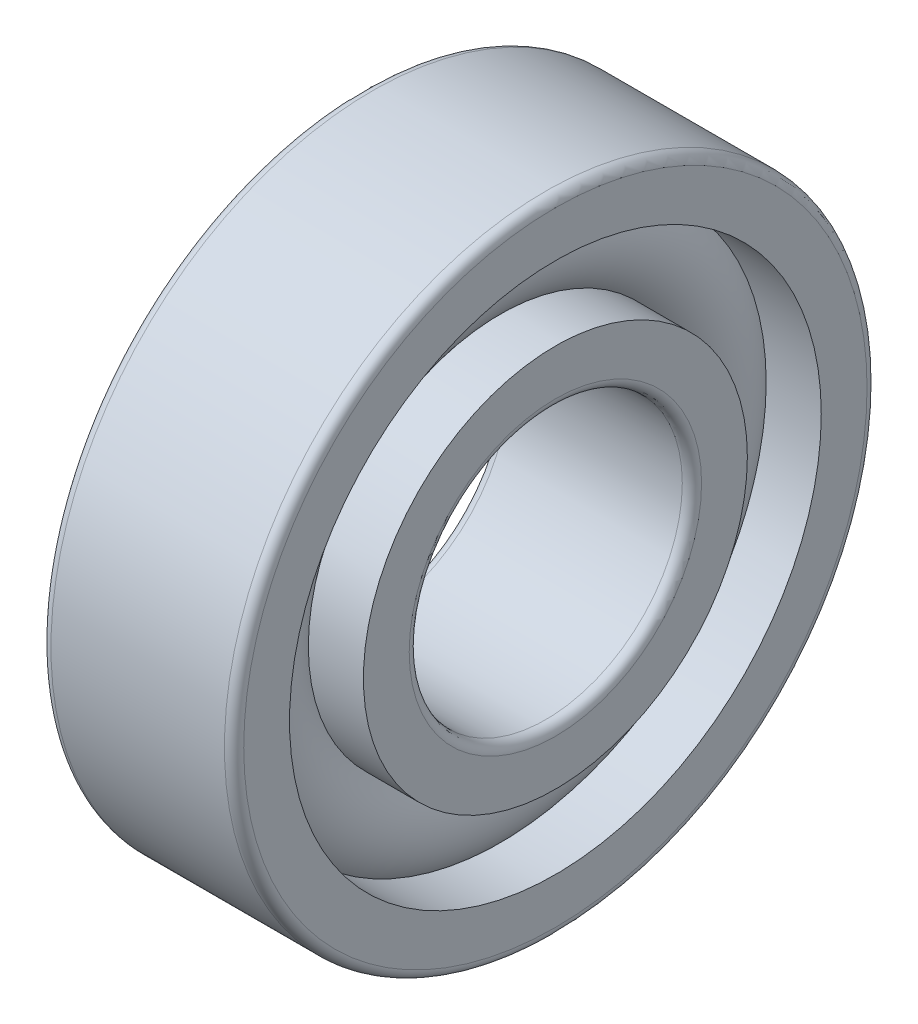
SolidWorks part; units mm, degrees
ref_plane "Plane1" through (0, 0, 0) normal (0, 0, 1) x (1, 0, 0)
ref_plane "Plane2" through (0, 0, 0) normal (0, 1, 0) x (1, 0, 0)
ref_plane "Plane3" through (0, 0, 0) normal (1, 0, 0) x (0, 0, -1)
sketch "Clipboard" plane through (0, 0, 0) normal (0, 0, 1) x (1, 0, 0)
  line L0 (-10, 0) -> (10, 0) construction
  line L1 (0, 0) -> (22.3471, -0.7804)
  line L2 (0, 0) -> (14.2413, 0.4973)
  line L3 (0, 0) -> (22.3471, -0.7804)
  line L4 (0, 0) -> (-22.3573, -0.3902)
  dimension "BallCLRad" = 14.25
sketch "CagSpiSke" plane through (0, 0, 0) normal (0, 0, 1) x (1, 0, 0)
  line L0 (0.345, 13.675) -> (0.345, 14.825)
  line L1 (0.345, 14.825) -> (-0.345, 14.825)
  line L2 (-0.345, 14.825) -> (-0.345, 13.675)
  line L3 (-0.345, 13.675) -> (0.345, 13.675)
  line L4 (-20.6375, 0) -> (20.6375, 0) construction
  line L5 (0, 0) -> (0, 23.7692) construction
  dimension "OD" = 29.65
  dimension "ID" = 27.35
revolve "CageSpine" add sketch "CagSpiSke" angle 0.001 about L4 reverse direction yes
ref_axis "Axis1" through (-50, 0, 0) along (1, 0, 0)
sketch "CagBalSke" plane through (0, 0, 0) normal (0, 0, 1) x (1, 0, 0)
  line L0 (-3.795, 14.25) -> (3.795, 14.25)
  line L1 (-1.905, 14.25) -> (1.905, 14.25) construction
  line L2 (-10, 0) -> (10, 0) construction
  line L3 (0, 0) -> (0, 24) construction
  arc A0 (3.795, 14.25) -> (-3.795, 14.25) centre (0, 14.25) cw
  dimension "BallCLRad" = 14.25
revolve "CageBall" [suppressed] add sketch "CagBalSke" angle 360 about L1 reverse direction yes
pattern_circular "CageBalls" [suppressed] count 2 every 180 about axis through (-50, 0, 0) along (1, 0, 0)
sketch "CagTrmODSke" plane through (0, 0, 0) normal (0, 0, 1) x (1, 0, 0)
  line L0 (3.796, 14.825) -> (3.796, 18.046)
  line L1 (3.796, 18.046) -> (-3.796, 18.046)
  line L2 (-3.796, 18.046) -> (-3.796, 14.825)
  line L3 (-3.796, 14.825) -> (3.796, 14.825)
  line L4 (-20.6375, 0) -> (20.6375, 0) construction
  line L5 (0, 0) -> (0, 25) construction
  dimension "Width" = 7.592
  dimension "ID" = 29.65
  dimension "OD" = 36.092
revolve "CageTrimOD" [suppressed] cut sketch "CagTrmODSke" angle 360 about L4 reverse direction yes
sketch "CagTrmIDSke" plane through (0, 0, 0) normal (0, 0, 1) x (1, 0, 0)
  line L0 (3.796, 10.456) -> (3.796, 13.675)
  line L1 (3.796, 13.675) -> (-3.796, 13.675)
  line L2 (-3.796, 13.675) -> (-3.796, 10.456)
  line L3 (-3.796, 10.456) -> (3.796, 10.456)
  line L4 (-20.6375, 0) -> (20.6375, 0) construction
  line L5 (0, 0) -> (0, 25) construction
  dimension "Width" = 7.592
  dimension "ID" = 20.912
  dimension "OD" = 27.35
revolve "CageTrimID" [suppressed] cut sketch "CagTrmIDSke" angle 360 about L4 reverse direction yes
sketch "BalSimSke" plane through (0, 0, 0) normal (0, 0, 1) x (1, 0, 0)
  line L0 (-10, 0) -> (10, 0) construction
  line L1 (-10, 14.25) -> (10, 14.25) construction
  line L2 (0, 0) -> (0, 23) construction
  circle A0 centre (0, 14.25) radius 3.45
  dimension "BallCLRad" = 14.25
  dimension "Ball_diameter" = 6.9
revolve "BallsSimplified" add sketch "BalSimSke" angle 360 about L0
sketch "BalDetSke" plane through (0, 0, 0) normal (0, 0, 1) x (1, 0, 0)
  line L0 (-3.45, 14.25) -> (3.45, 14.25)
  line L1 (-1.905, 14.25) -> (1.905, 14.25) construction
  line L2 (0, 0) -> (0, 25) construction
  arc A0 (3.45, 14.25) -> (-3.45, 14.25) centre (0, 14.25) cw
  dimension "BallCLRad" = 14.25
  dimension "Ball_diameter" = 6.9
revolve "BallDetailed" [suppressed] add sketch "BalDetSke" angle 360 about L1 reverse direction yes
sketch "InnRacSke" plane through (0, 0, 0) normal (0, 0, 1) x (1, 0, 0)
  line L0 (-2.5378, 11.95) -> (-6, 11.95)
  line L1 (-6, 11.95) -> (-6, 9.1)
  line L2 (-5.4, 8.5) -> (5.4, 8.5)
  line L3 (6, 9.1) -> (6, 11.95)
  line L4 (6, 11.95) -> (2.5378, 11.95)
  line L5 (-20.6375, 0) -> (20.6375, 0) construction
  line L6 (0, 0) -> (0, 30) construction
  arc A0 (-6, 9.1) -> (-5.4, 8.5) centre (-5.4, 9.1) ccw
  arc A1 (5.4, 8.5) -> (6, 9.1) centre (5.4, 9.1) ccw
  arc A2 (2.5378, 11.95) -> (-2.5378, 11.95) centre (0, 14.25) cw
  dimension "BallCLRad" = 14.25
  dimension "Fillet_radius" = 0.6
  dimension "Ball_diameter" = 6.85
  dimension "ID" = 17
  dimension "OD" = 23.9
  dimension "Width" = 12
revolve "InnerRace" add sketch "InnRacSke" angle 360 about L5 reverse direction yes
sketch "OutRacSke" plane through (0, 0, 0) normal (0, 0, 1) x (1, 0, 0)
  line L0 (-2.5378, 16.55) -> (-6, 16.55)
  line L1 (-6, 16.55) -> (-6, 19.4)
  line L2 (-5.4, 20) -> (5.4, 20)
  line L3 (6, 19.4) -> (6, 16.55)
  line L4 (6, 16.55) -> (2.5378, 16.55)
  line L5 (-20.6375, 0) -> (20.6375, 0) construction
  line L6 (0, 0) -> (0, 30) construction
  arc A0 (-6, 19.4) -> (-5.4, 20) centre (-5.4, 19.4) cw
  arc A1 (5.4, 20) -> (6, 19.4) centre (5.4, 19.4) cw
  arc A2 (2.5378, 16.55) -> (-2.5378, 16.55) centre (0, 14.25) ccw
  dimension "BallCLRad" = 14.25
  dimension "Fillet_radius" = 0.6
  dimension "Ball_diameter" = 6.85
  dimension "Width" = 12
revolve "OuterRace" add sketch "OutRacSke" angle 360 about L5 reverse direction yes
pattern_circular "BallsDetailed" [suppressed] count 2 every 180 about axis through (-50, 0, 0) along (1, 0, 0)
other "Freeze***"
equation "\"BallCLRad@Clipboard\" = ( \"OD@OutRacSke\" + \"ID@InnRacSke\" ) / 4"
equation "\"BallCLRad@BalSimSke\" = \"BallCLRad@Clipboard\""
equation "\"BallCLRad@BalDetSke\" = \"BallCLRad@Clipboard\""
equation "\"BallCLRad@InnRacSke\" = \"BallCLRad@Clipboard\""
equation "\"BallCLRad@OutRacSke\" = \"BallCLRad@Clipboard\""
equation "\"Ball_diameter@InnRacSke\" = \"Ball_diameter@BalDetSke\" - 0.05"
equation "\"Ball_diameter@OutRacSke\" = \"Ball_diameter@BalDetSke\" - 0.05"
equation "\"Ball_diameter@BalSimSke\" = \"Ball_diameter@BalDetSke\""
equation "\"Width@OutRacSke\" = \"Width@InnRacSke\""
equation "\"Fillet_radius@OutRacSke\" = \"Fillet_radius@InnRacSke\""
equation "\"Max_count@Clipboard\" = int( 3.14159265 / atn(( \"Ball_diameter@BalDetSke\" / 2) / sqr( \"BallCLRad@Clipboard\"  *  \"BallCLRad@Clipboard\" - ( \"Ball_diameter@BalDetSke\" / 2) *  ( \"Ball_diameter@BalDetSke\" / 2))))"
equation "\"Max_count@Clipboard\" = ((sgn( \"Max_count@Clipboard\" - \"Count@Clipboard\" )-1)*( \"Max_count@Clipboard\" - \"Count@Clipboard\" ))/-2+ \"Count@Clipboard\""
equation "\"Count@BallsDetailed\" = int( \"Show_count@Clipboard\" ) "
equation "\"Count@BallsDetailed\" = ((sgn( \"Count@BallsDetailed\" - \"Max_count@Clipboard\" )-1)*( \"Count@BallsDetailed\" - \"Max_count@Clipboard\" ))/-2+ \"Max_count@Clipboard\""
equation "\"Count@BallsDetailed\" = ((sgn( \"Count@BallsDetailed\" - \"Min_count@Clipboard\" )+1)*( \"Count@BallsDetailed\" - \"Min_count@Clipboard\"))/2 +\"Min_count@Clipboard\""
equation "\"Angle@BallsDetailed\" = 360.0 / \"Max_count@Clipboard\""
equation "\"BallCLRad@CagBalSke\" = \"BallCLRad@Clipboard\""
equation "\"Count@CageBalls\" = \"Count@BallsDetailed\""
equation "\"Angle@CageBalls\" = \"Angle@BallsDetailed\""
equation "\"Angle@CageSpine\" =  \"Angle@CageBalls\" * ( \"Count@CageBalls\" -1 + int( \"Count@CageBalls\" / \"Max_count@Clipboard\" ) )  + 0.001 -  int( \"Count@CageBalls\" / \"Max_count@Clipboard\" ) * 0.001"
equation "\"Angle@CageSpine\" =  \"Angle@CageSpine\" * int( \"Min_count@Clipboard\" / 2) + int(1 / \"Min_count@Clipboard\")  * 0.001"
equation "\"CageWallOD@CagBalSke\" =  \"Ball_diameter@BalDetSke\" * 1.1"
equation "\"Thickness@CagSpiSke\" =  \"Ball_diameter@BalDetSke\" * 0.1"
equation "\"OD@CagTrmODSke\" = \"BallCLRad@Clipboard\" * 2 + \"CageWallOD@CagBalSke\" + 0.002"
equation "\"ID@CagTrmODSke\" = \"BallCLRad@Clipboard\" * 2 + \"Ball_diameter@BalDetSke\" / 6"
equation "\"OD@CagTrmIDSke\" = \"BallCLRad@Clipboard\" * 2 - \"Ball_diameter@BalDetSke\" / 6"
equation "\"ID@CagTrmIDSke\" = \"BallCLRad@Clipboard\" * 2 - \"CageWallOD@CagBalSke\" + 0.002"
equation "\"OD@CagSpiSke\" = \"ID@CagTrmODSke\""
equation "\"ID@CagSpiSke\" = \"OD@CagTrmIDSke\""
equation "\"Width@CagTrmODSke\" = \"CageWallOD@CagBalSke\" + 0.002"
equation "\"Width@CagTrmIDSke\" = \"CageWallOD@CagBalSke\" + 0.002"
